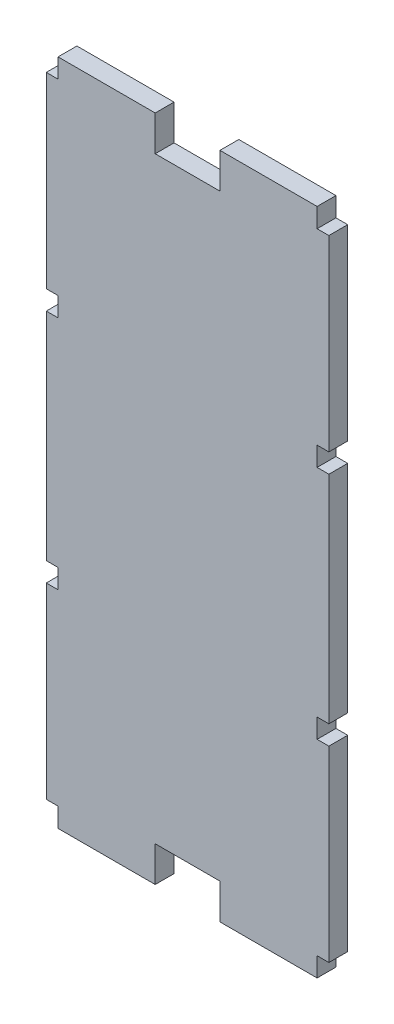
SolidWorks part; units mm, degrees
material "Pine"
ref_plane "Front Plane" through (0, 0, 0) normal (0, 0, 1) x (1, 0, 0)
ref_plane "Top Plane" through (0, 0, 0) normal (0, 1, 0) x (1, 0, 0)
ref_plane "Right Plane" through (0, 0, 0) normal (1, 0, 0) x (0, 0, -1)
sketch "Sketch1" plane through (0, 0, 0) normal (0, 0, 1) x (1, 0, 0)
  line L1 (-38.1, -90.0906) -> (38.1, -90.0906)
  line L2 (-38.1, -90.0906) -> (-38.1, 90.0906)
  line L3 (-38.1, 90.0906) -> (38.1, 90.0906)
  line L4 (38.1, -90.0906) -> (38.1, 90.0906)
  line L5 (-38.1, -90.0906) -> (38.1, 90.0906) construction
  line L6 (-38.1, 90.0906) -> (38.1, -90.0906) construction
  point P0 (0, 0)
  dimension "D1" = 180.1812
  dimension "D2" = 76.2
extrude "Boss-Extrude1" add sketch "Sketch1" along normal blind 5.08
sketch "Sketch3" plane through (0, 0, 5.08) normal (0, 0, 1) x (1, 0, 0)
  line L6 (0, 0) -> (60.4565, 0) construction
  line L11 (0, 0) -> (0, 20.8202) construction
  line L20 (-8.7312, -90.0906) -> (-8.7312, -80.5656)
  line L21 (-38.1, -90.0906) -> (38.1, -90.0906) construction
  line L22 (-8.7312, -80.5656) -> (8.7312, -80.5656)
  line L23 (8.7312, -80.5656) -> (8.7312, -90.0906)
  line L24 (8.7312, -90.0906) -> (-8.7312, -90.0906)
  line L25 (8.7312, 90.0906) -> (-8.7312, 90.0906)
  line L26 (8.7312, 80.5656) -> (8.7312, 90.0906)
  line L27 (-8.7312, 80.5656) -> (8.7312, 80.5656)
  line L28 (-8.7312, 90.0906) -> (-8.7312, 80.5656)
  point P30 (0, -80.5656)
  dimension "D4" = 17.4625
  dimension "D5" = 9.525
extrude "Cut-Extrude1" cut sketch "Sketch3" against normal through all
sketch "Sketch4" plane through (0, 0, 5.08) normal (0, 0, 1) x (1, 0, 0)
  line L0 (34.925, 90.0906) -> (34.925, 84.8836)
  line L1 (38.1, 90.0906) -> (8.7312, 90.0906) construction
  line L2 (34.925, 84.8836) -> (38.1, 84.8836)
  line L3 (38.1, -90.0906) -> (38.1, 90.0906) construction
  line L4 (34.925, 90.0906) -> (38.1, 90.0906)
  line L5 (38.1, 90.0906) -> (38.1, 84.8836)
  line L6 (0, 0) -> (63.5, 0) construction
  line L7 (0, 0) -> (0, 111.7273) construction
  line L8 (-38.1, 90.0906) -> (-38.1, 84.8836)
  line L9 (-34.925, 90.0906) -> (-38.1, 90.0906)
  line L10 (-34.925, 84.8836) -> (-38.1, 84.8836)
  line L11 (-34.925, 90.0906) -> (-34.925, 84.8836)
  line L12 (-34.925, -90.0906) -> (-34.925, -84.8836)
  line L13 (-34.925, -84.8836) -> (-38.1, -84.8836)
  line L14 (-34.925, -90.0906) -> (-38.1, -90.0906)
  line L15 (-38.1, -90.0906) -> (-38.1, -84.8836)
  line L16 (38.1, -90.0906) -> (38.1, -84.8836)
  line L17 (34.925, -90.0906) -> (38.1, -90.0906)
  line L18 (34.925, -84.8836) -> (38.1, -84.8836)
  line L19 (34.925, -90.0906) -> (34.925, -84.8836)
  line L20 (38.1, 34.3535) -> (34.925, 34.3535)
  line L21 (34.925, 34.3535) -> (34.925, 29.1465)
  line L22 (34.925, 29.1465) -> (38.1, 29.1465)
  line L23 (38.1, 29.1465) -> (38.1, 34.3535)
  line L25 (38.1, -29.1465) -> (38.1, -34.3535)
  line L26 (34.925, -29.1465) -> (38.1, -29.1465)
  line L27 (34.925, -34.3535) -> (34.925, -29.1465)
  line L28 (38.1, -34.3535) -> (34.925, -34.3535)
  line L29 (-38.1, -34.3535) -> (-34.925, -34.3535)
  line L30 (-34.925, -34.3535) -> (-34.925, -29.1465)
  line L31 (-34.925, -29.1465) -> (-38.1, -29.1465)
  line L32 (-38.1, -29.1465) -> (-38.1, -34.3535)
  line L33 (-38.1, 29.1465) -> (-38.1, 34.3535)
  line L34 (-34.925, 29.1465) -> (-38.1, 29.1465)
  line L35 (-34.925, 34.3535) -> (-34.925, 29.1465)
  line L36 (-38.1, 34.3535) -> (-34.925, 34.3535)
  point P27 (38.1, 31.75)
  dimension "D1" = 5.207
  dimension "D2" = 3.175
  dimension "D3" = 31.75
extrude "Cut-Extrude2" cut sketch "Sketch4" against normal through all
